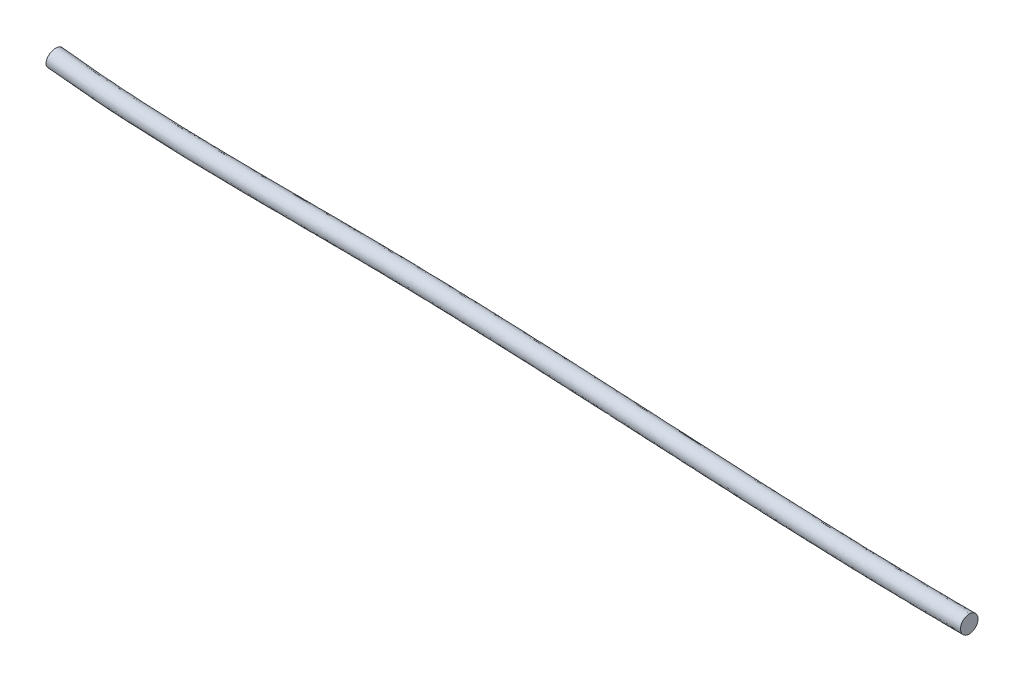
SolidWorks part; units mm, degrees
ref_plane "Front Plane" through (0, 0, 0) normal (0, 0, 1) x (1, 0, 0)
ref_plane "Top Plane" through (0, 0, 0) normal (0, 1, 0) x (1, 0, 0)
ref_plane "Right Plane" through (0, 0, 0) normal (1, 0, 0) x (0, 0, -1)
sketch "Sketch1" plane through (0, 0, 0) normal (0, 0, 1) x (1, 0, 0)
  spline S0 degree 3 poles (-45.0249, 7.078) (-44.3938, 7.0037) (-42.6479, 7.0571) (-40.9086, 6.8888) (-39.798, 6.8869) knots 0 0 0 0 0.363389 1 1 1 1
sweep "Sweep1" add path "Sketch1" circular profile diameter 0.1 parameters "D3"=0.1
ref_plane "Plane1" through (-40.2656, 4.74, 0) normal (-0.9931, 0.1169, 0) x (0, 0, 1)
